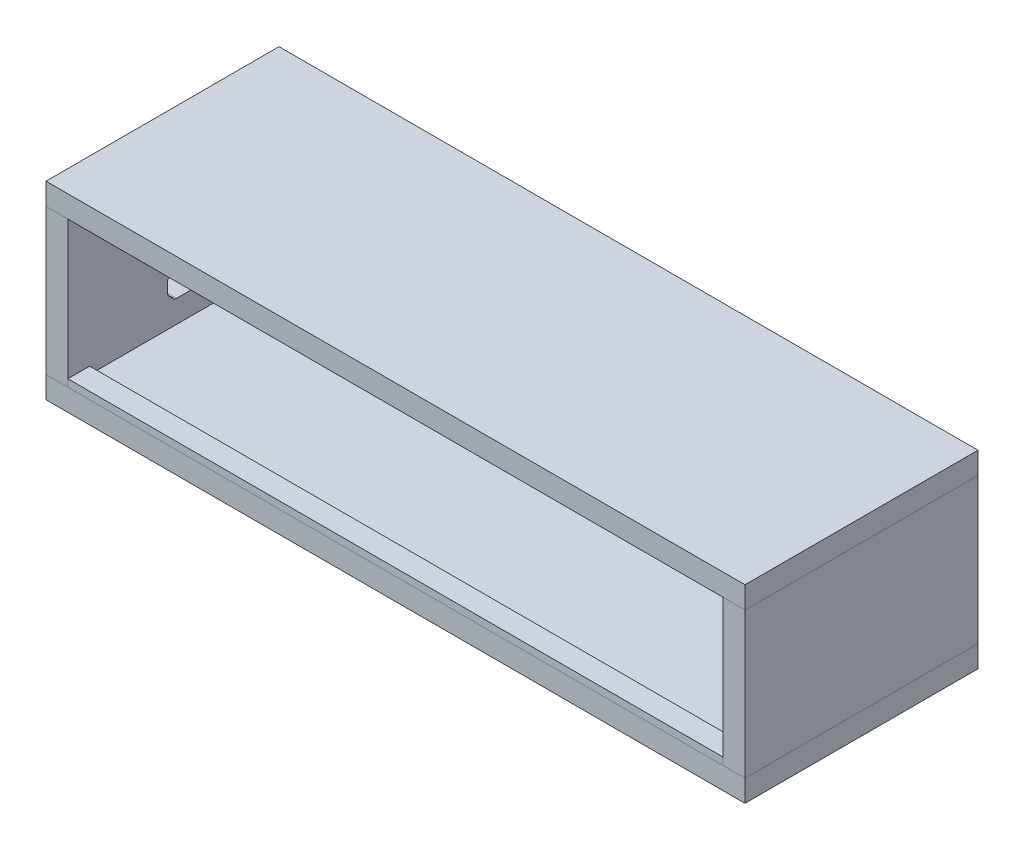
SolidWorks part; units mm, degrees
ref_plane "Front Plane" through (0, 0, 0) normal (0, 0, 1) x (1, 0, 0)
ref_plane "Top Plane" through (0, 0, 0) normal (0, 1, 0) x (1, 0, 0)
ref_plane "Right Plane" through (0, 0, 0) normal (1, 0, 0) x (0, 0, -1)
sketch "Sketch1" plane through (0, 0, 0) normal (0, 1, 0) x (1, 0, 0)
  line L1 (-304.8, 101.6) -> (304.8, 101.6)
  line L2 (-304.8, 101.6) -> (-304.8, -101.6)
  line L3 (-304.8, -101.6) -> (304.8, -101.6)
  line L4 (304.8, 101.6) -> (304.8, -101.6)
  line L5 (-304.8, 101.6) -> (304.8, -101.6) construction
  line L6 (-304.8, -101.6) -> (304.8, 101.6) construction
  point P0 (0, 0)
  dimension "D1" = 609.6
  dimension "D2" = 203.2
extrude "Boss-Extrude1" add sketch "Sketch1" along normal blind 19.05
sketch "Sketch2" plane through (0, 19.05, 0) normal (0, 1, 0) x (1, 0, 0)
  line L0 (-304.8, -101.6) -> (304.8, -101.6) construction
  line L1 (-304.8, 101.6) -> (-285.75, 101.6)
  line L2 (-304.8, 101.6) -> (-304.8, -101.6)
  line L3 (-304.8, -101.6) -> (-285.75, -101.6)
  line L4 (-285.75, 101.6) -> (-285.75, -101.6)
  line L5 (304.8, 101.6) -> (-304.8, 101.6) construction
  line L6 (304.8, -101.6) -> (285.75, -101.6)
  line L7 (304.8, -101.6) -> (304.8, 101.6)
  line L8 (304.8, 101.6) -> (285.75, 101.6)
  line L9 (285.75, -101.6) -> (285.75, 101.6)
  line L11 (-285.75, 101.6) -> (285.75, 101.6)
  line L12 (-285.75, 101.6) -> (-285.75, 82.55)
  line L13 (-285.75, 82.55) -> (285.75, 82.55)
  line L14 (285.75, 101.6) -> (285.75, 82.55)
  line M7 (304.8, -101.6) -> (304.8, 101.6)
  line M8 (304.8, 101.6) -> (-304.8, 101.6)
  line M9 (-304.8, 101.6) -> (-304.8, -101.6)
  line M10 (-304.8, -101.6) -> (304.8, -101.6)
  dimension "D1" = 19.05
  dimension "D2" = 19.05
  dimension "D3" = 19.05
extrude "Boss-Extrude2" add sketch "Sketch2" along normal blind 127 separate body contours L4 M8 M9 M10 | L9 M10 M7 M8 region at (-295.275, 19.05, 0) region at (295.275, 19.05, 0)
extrude "Boss-Extrude3" add sketch "Sketch2<3>" along normal up to surface (127 mm away) separate body contours L4 L13 L9 M8 region at (0, 19.05, -92.075) up to face at (-295.275, 146.05, 0)
sketch "Sketch2<3>" plane through (0, 19.05, 0) normal (0, 1, 0) x (1, 0, 0) same geometry as "Sketch2"
sketch "Sketch3" plane through (0, 146.05, 0) normal (0, 1, 0) x (1, 0, 0)
  line L1 (-304.8, 101.6) -> (304.8, 101.6)
  line L2 (-304.8, 101.6) -> (-304.8, -101.6)
  line L3 (-304.8, -101.6) -> (304.8, -101.6)
  line L4 (304.8, 101.6) -> (304.8, -101.6)
extrude "Boss-Extrude4" add sketch "Sketch3" along normal blind 19.05 separate body
sketch "Sketch4" plane through (0, 19.05, 0) normal (0, 1, 0) x (1, 0, 0)
  line L0 (285.75, -101.6) -> (285.75, 101.6) construction
  line L1 (-285.75, -101.6) -> (285.75, -101.6)
  line L2 (-285.75, -101.6) -> (-285.75, -82.55)
  line L3 (-285.75, -82.55) -> (285.75, -82.55)
  line L4 (285.75, -101.6) -> (285.75, -82.55)
  dimension "D1" = 19.05
extrude "Boss-Extrude5" add sketch "Sketch4" along normal blind 6.35 separate body
sketch "Sketch5" plane through (-304.8, 0, -304.8) normal (1, 0, 0) x (0, 0, -1)
  line L0 (-203.2, 82.55) -> (-406.4, 82.55) construction
  line L1 (-203.2, 146.05) -> (-203.2, 19.05) construction
  line L2 (-406.4, 146.05) -> (-406.4, 19.05) construction
  line L3 (-304.8, 82.55) -> (-304.8, 19.05) construction
  line L4 (-203.2, 19.05) -> (-406.4, 19.05) construction
  line L26 (-295.1743, 39.8975) -> (-291.0923, 43.9795)
  line L27 (-289.9361, 46.7691) -> (-289.9361, 54.4059)
  line L28 (-295.9636, 60.4385) -> (-313.5841, 60.4385)
  line L29 (-319.6321, 54.3905) -> (-319.6321, 46.8124)
  line L30 (-318.4465, 43.95) -> (-314.4246, 39.9281)
  line L31 (-311.5622, 38.7425) -> (-309.7841, 38.7425)
  line L32 (-309.7841, 38.7425) -> (-299.7841, 38.7425)
  line L33 (-299.7841, 38.7425) -> (-297.9644, 38.7425)
  spline S18 degree 3 poles (-291.0923, 43.9795) (-291.0033, 44.0735) (-290.9158, 44.1689) (-290.7535, 44.3694) (-290.6774, 44.4737) (-290.4636, 44.7979) (-290.3426, 45.0263) (-290.1465, 45.4989) (-290.0705, 45.7454) (-289.9923, 46.1261) (-289.9724, 46.2537) (-289.9454, 46.5104) (-289.9398, 46.6397) (-289.9361, 46.7691) knots 0 0 0 0 0.125 0.125 0.25 0.25 0.5 0.5 0.75 0.75 0.875 0.875 1 1 1 1
  spline S19 degree 3 poles (-289.9361, 54.4059) (-289.9381, 54.6045) (-289.9467, 54.8019) (-289.9861, 55.1929) (-290.0151, 55.3868) (-290.0921, 55.7711) (-290.1401, 55.9616) (-290.2552, 56.3393) (-290.3228, 56.5272) (-290.5499, 57.0745) (-290.7344, 57.4205) (-291.1705, 58.0741) (-291.4251, 58.3841) (-291.9809, 58.9409) (-292.2833, 59.191) (-292.7753, 59.5217) (-292.9465, 59.6247) (-293.2946, 59.8114) (-293.4723, 59.8957) (-294.0155, 60.1225) (-294.3917, 60.2394) (-294.9766, 60.3577) (-295.1726, 60.3872) (-295.5666, 60.4274) (-295.7648, 60.4358) (-295.9636, 60.4385) knots 0 0 0 0 0.0625 0.0625 0.125 0.125 0.1875 0.1875 0.25 0.25 0.375 0.375 0.5 0.5 0.625 0.625 0.6875 0.6875 0.75 0.75 0.875 0.875 0.9375 0.9375 1 1 1 1
  spline S20 degree 3 poles (-313.5841, 60.4385) (-313.9834, 60.4385) (-314.376, 60.3998) (-314.9552, 60.2847) (-315.1466, 60.2368) (-315.5262, 60.1217) (-315.7149, 60.0541) (-316.2641, 59.827) (-316.6115, 59.6419) (-317.2686, 59.2036) (-317.5795, 58.9479) (-318.1377, 58.3905) (-318.3886, 58.0866) (-318.7204, 57.5913) (-318.8233, 57.4195) (-319.0098, 57.0704) (-319.094, 56.8921) (-319.3205, 56.3466) (-319.4373, 55.9666) (-319.5935, 55.185) (-319.6321, 54.7899) (-319.6321, 54.3905) knots 0 0 0 0 0.125 0.125 0.1875 0.1875 0.25 0.25 0.375 0.375 0.5 0.5 0.625 0.625 0.6875 0.6875 0.75 0.75 0.875 0.875 1 1 1 1
  spline S21 degree 3 poles (-319.6321, 46.8124) (-319.6321, 46.5457) (-319.6061, 46.2818) (-319.5017, 45.7593) (-319.4244, 45.5064) (-319.2237, 45.0204) (-319.0984, 44.7849) (-318.8033, 44.3432) (-318.6351, 44.1386) (-318.4465, 43.95) knots 0 0 0 0 0.25 0.25 0.5 0.5 0.75 0.75 1 1 1 1
  spline S22 degree 3 poles (-314.4246, 39.9281) (-314.236, 39.7395) (-314.0309, 39.5713) (-313.5877, 39.2757) (-313.3542, 39.1515) (-312.8686, 38.9498) (-312.6135, 38.8719) (-312.0925, 38.7682) (-311.8289, 38.7425) (-311.5622, 38.7425) knots 0 0 0 0 0.25 0.25 0.5 0.5 0.75 0.75 1 1 1 1
  spline S23 degree 3 poles (-297.9644, 38.7425) (-297.8349, 38.746) (-297.7057, 38.7516) (-297.4491, 38.7786) (-297.3215, 38.7985) (-296.9411, 38.8766) (-296.6941, 38.9525) (-296.2213, 39.1481) (-295.9932, 39.2686) (-295.6687, 39.4825) (-295.5644, 39.5587) (-295.3638, 39.7211) (-295.2684, 39.8086) (-295.1743, 39.8975) knots 0 0 0 0 0.125 0.125 0.25 0.25 0.5 0.5 0.75 0.75 0.875 0.875 1 1 1 1
  point P11 (-304.7739, 60.4385)
  point P13 (0, 0)
extrude "Cut-Extrude1" cut sketch "Sketch5" along normal up to surface (19.05 mm away) up to face at (-285.75, 82.55, 0)
